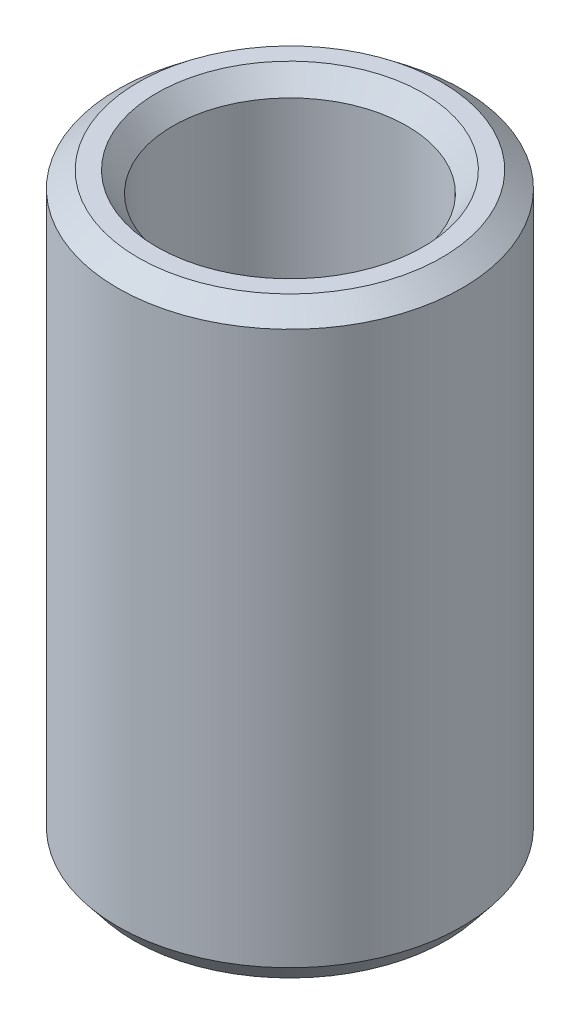
SolidWorks part; units mm, degrees
ref_plane "Front Plane" through (0, 0, 0) normal (0, 0, 1) x (1, 0, 0)
ref_plane "Top Plane" through (0, 0, 0) normal (0, 1, 0) x (1, 0, 0)
ref_plane "Right Plane" through (0, 0, 0) normal (1, 0, 0) x (0, 0, -1)
sketch "Sketch1" plane through (0, 0, 0) normal (0, 1, 0) x (1, 0, 0)
  circle A0 centre (0, 0) radius 40
  dimension "SLEEVE_OD" = 80
extrude "Boss-Extrude1" add sketch "Sketch1" along normal blind 136.9173
sketch "Sketch2" plane through (0, 0, 0) normal (0, 1, 0) x (1, 0, 0)
  circle A0 centre (0, 0) radius 27.1829
  dimension "BORE_D" = 54.3658
extrude "Cut-Extrude1" cut sketch "Sketch2" along normal through all
chamfer "Chamfer1" distance 3.7727 angle 51.406 4 edges at (0, 136.9173, 27.1829) (0, 0, 27.1829) (0, 0, 40) (0, 136.9173, 40) first distance on face at (0, 136.9173, 27.1829) first distance on face at (0, 0, 27.1829) first distance on face at (0, 136.9173, 40)
